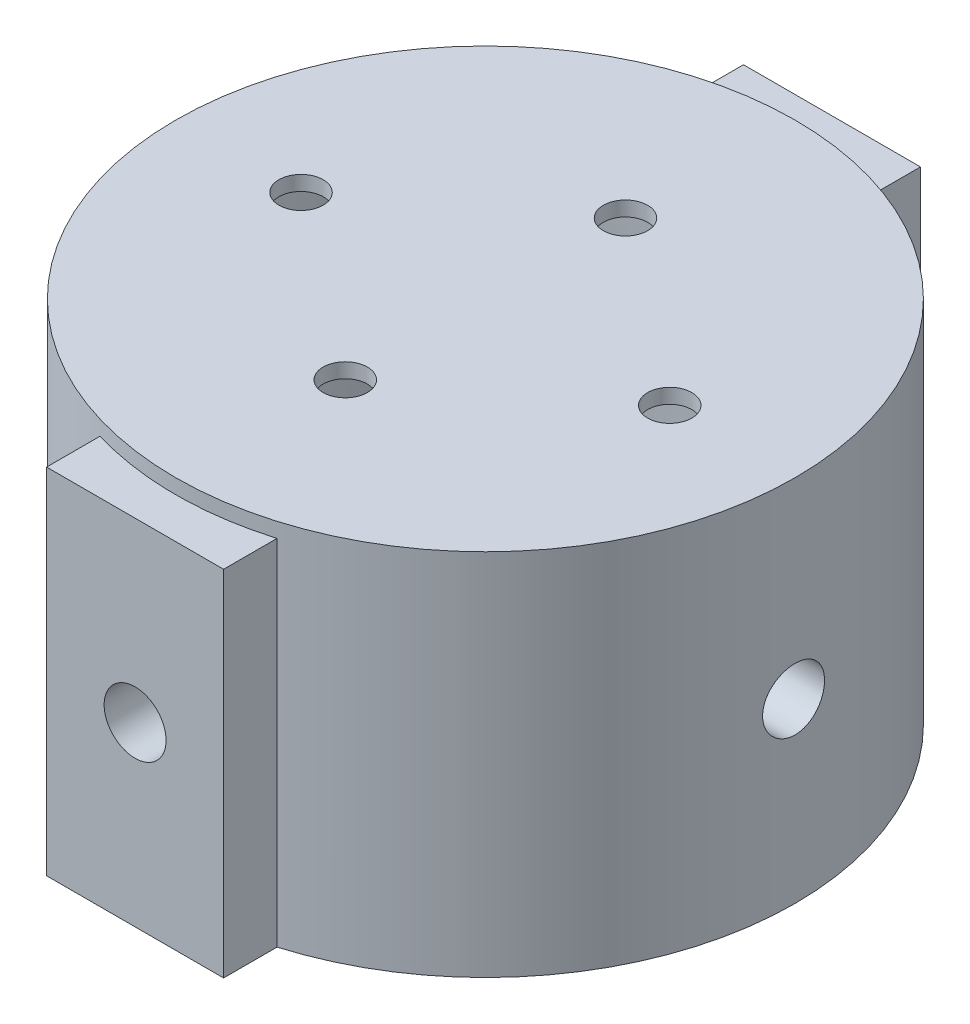
SolidWorks part; units mm, degrees
ref_plane "Front Plane" through (0, 0, 0) normal (0, 0, 1) x (1, 0, 0)
ref_plane "Top Plane" through (0, 0, 0) normal (0, 1, 0) x (1, 0, 0)
ref_plane "Right Plane" through (0, 0, 0) normal (1, 0, 0) x (0, 0, -1)
sketch "Sketch1" plane through (0, 0, 0) normal (0, 1, 0) x (1, 0, 0)
  circle A0 centre (0, 0) radius 17.75
  circle A1 centre (0, 0) radius 21
  dimension "D1" = 35.5
  dimension "D2" = 42
extrude "Boss-Extrude2" add sketch "Sketch1" along normal mid plane 24
sketch "Sketch5" plane through (0, 0, 0) normal (0, 1, 0) x (1, 0, 0)
  line L1 (-6, 17.5) -> (6, 17.5)
  line L2 (-6, 17.5) -> (-6, 23.5)
  line L3 (-6, 23.5) -> (6, 23.5)
  line L4 (6, 17.5) -> (6, 23.5)
  line L5 (-6, 17.5) -> (6, 23.5) construction
  line L6 (-6, 23.5) -> (6, 17.5) construction
  point P0 (0, 20.5)
  point P6 (0, 0)
  point P7 (0, 0)
  point P8 (0, 0)
  dimension "D1" = 12
  dimension "D2" = 6
extrude "Boss-Extrude7" add sketch "Sketch5" along normal mid plane 24 separate body
sketch "Sketch6" plane through (0, 0, 0) normal (0, 1, 0) x (1, 0, 0)
  line L1 (-6, -17.75) -> (6, -17.75)
  line L2 (-6, -17.75) -> (-6, -23.75)
  line L3 (-6, -23.75) -> (6, -23.75)
  line L4 (6, -17.75) -> (6, -23.75)
  line L5 (-6, -17.75) -> (6, -23.75) construction
  line L6 (-6, -23.75) -> (6, -17.75) construction
  circle A0 centre (0, 0) radius 17.75 construction
  point P0 (0, -20.75)
  point P5 (0, 0)
  point P7 (0, 0)
  dimension "D1" = 12
  dimension "D2" = 6
extrude "Boss-Extrude8" add sketch "Sketch6" along normal mid plane 24
sketch "Sketch7" plane through (0, 0, -23.5) normal (0, 0, -1) x (-1, 0, 0)
  circle A0 centre (0, 0) radius 2.1
  dimension "D1" = 4.2
extrude "Cut-Extrude1" cut sketch "Sketch7" against normal through all
sketch "Sketch8" plane through (0, 12, 0) normal (0, 1, 0) x (1, 0, 0)
  circle A0 centre (0, 0) radius 21
  dimension "D1" = 42
extrude "Boss-Extrude9" add sketch "Sketch8" along normal blind 1
sketch "Sketch9" plane through (0, 13, 0) normal (0, 1, 0) x (1, 0, 0)
  circle A0 centre (0, 0) radius 9.5 construction
  circle A2 centre (0, 9.5) radius 1.5
  circle A3 centre (0, -9.5) radius 1.5
  circle A4 centre (0, 0) radius 12.5 construction
  circle A5 centre (-12.5, 0) radius 1.5
  circle A6 centre (12.5, 0) radius 1.5
  dimension "D1" = 19
  dimension "D2" = 3
  dimension "D3" = 3
  dimension "D4" = 25
  dimension "D5" = 3
  dimension "D6" = 3
extrude "Cut-Extrude2" cut sketch "Sketch9" against normal up to next
sketch "Sketch10" plane through (-6, 0, 0) normal (-1, 0, 0) x (0, 0, 1)
  circle A0 centre (0, 0) radius 2.1
  dimension "D1" = 4.2
extrude "Cut-Extrude3" cut sketch "Sketch10" against normal through all and the other way through all
